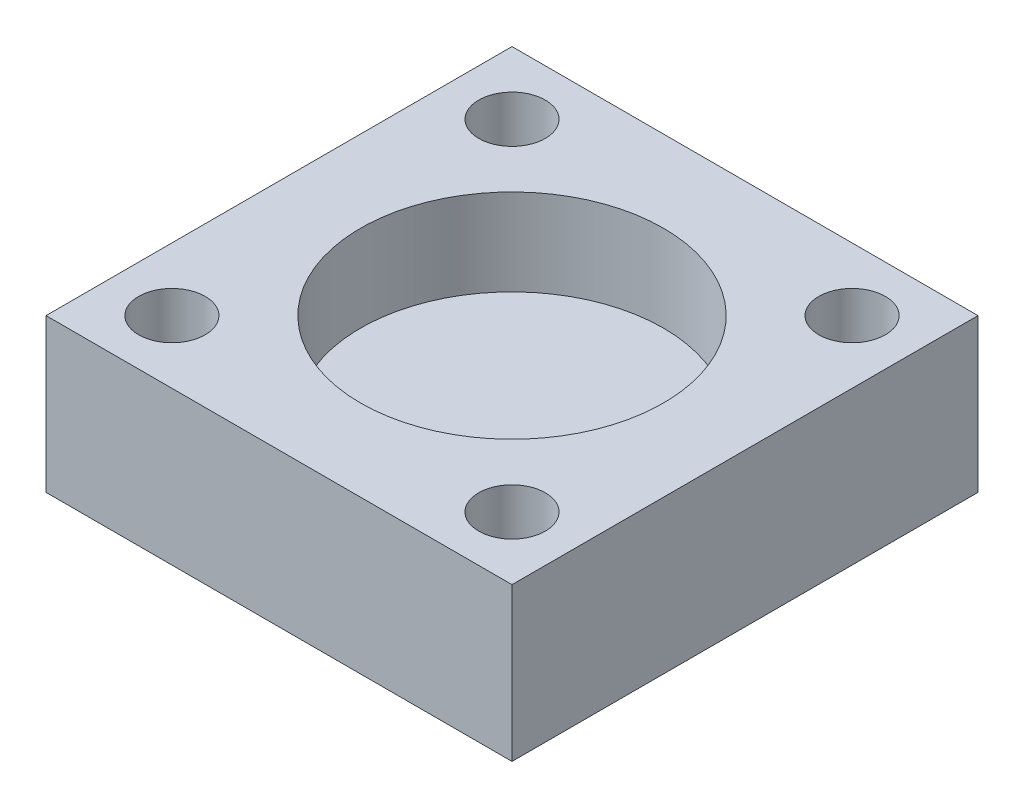
SolidWorks part; units mm, degrees
ref_plane "Front Plane" through (0, 0, 0) normal (0, 0, 1) x (1, 0, 0)
ref_plane "Top Plane" through (0, 0, 0) normal (0, 1, 0) x (1, 0, 0)
ref_plane "Right Plane" through (0, 0, 0) normal (1, 0, 0) x (0, 0, -1)
sketch "Sketch2" plane through (0, 0, 0) normal (0, 1, 0) x (1, 0, 0)
  line L1 (14, 14) -> (-14, 14)
  line L2 (14, 14) -> (14, -14)
  line L3 (14, -14) -> (-14, -14)
  line L4 (-14, 14) -> (-14, -14)
  line L5 (14, 14) -> (-14, -14) construction
  line L6 (14, -14) -> (-14, 14) construction
  circle A0 centre (0, 0) radius 9.1
  point P0 (0, 0)
  dimension "D1" = 18.2
  dimension "D3" = 14
extrude "Boss-Extrude1" add sketch "Sketch2" along normal blind 5.2 contours L1 L4 L3 L2 A0 | A0 | L2 L1 L4 L3 region at (13.604, 0, 0)
extrude "Boss-Extrude2" add sketch "Sketch2<4>" against normal blind 4 contours A0 | L1 L4 L3 L2 A0 region at (13.604, 0, 0) region at (0, 0, 0)
sketch "Sketch2<4>" plane through (0, 0, 0) normal (0, 1, 0) x (1, 0, 0) same geometry as "Sketch2"
sketch "Sketch3" plane through (0, 5.2, 0) normal (0, 1, 0) x (1, 0, 0)
  line L0 (-14, 14) -> (-6.4347, 6.4347) construction
  line L1 (0, 14) -> (0, -14) construction
  line L2 (-14, 0) -> (14, 0) construction
  line L4 (14, 14) -> (-14, 14)
  line L5 (-14, 14) -> (-14, -14)
  line L6 (-14, -14) -> (14, -14)
  line L7 (14, -14) -> (14, 14)
  line L8 (14, 14) -> (-14, 14)
  line L9 (-14, 14) -> (-14, -14)
  line L10 (-14, -14) -> (14, -14)
  line L11 (14, -14) -> (14, 14)
  circle A0 centre (0, 0) radius 9.1 construction
  circle A1 centre (0, 0) radius 9.1
  circle A2 centre (-10.2173, 10.2173) radius 2
  circle A3 centre (-10.2173, -10.2173) radius 2
  circle A4 centre (10.2173, -10.2173) radius 2
  circle A5 centre (10.2173, 10.2173) radius 2
  dimension "D2" = 4
  dimension "D1" = 0
extrude "Cut-Extrude1" cut sketch "Sketch3" against normal through all contours A4 | A3 | A2 | A5 region at (-10.2173, 5.2, -10.2173) region at (-10.2173, 5.2, 10.2173) region at (10.2173, 5.2, 10.2173) region at (10.2173, 5.2, -10.2173)
sketch "Sketch4" plane through (0, 5.2, 0) normal (0, 1, 0) x (1, 0, 0)
  line L0 (-14, 0) -> (14, 0) construction
  line L1 (-14, 14) -> (-14, -14) construction
  line L2 (14, 14) -> (14, -14) construction
  line L3 (0, 14) -> (0, -14) construction
  line L4 (14, 14) -> (-14, 14) construction
  line L5 (14, -14) -> (-14, -14) construction
  circle A0 centre (10.2173, 10.2173) radius 2 construction
  circle A1 centre (10.2173, -10.2173) radius 2 construction
  circle A2 centre (-10.2173, -10.2173) radius 2 construction
  circle A3 centre (-10.2173, 10.2173) radius 2 construction
  circle A4 centre (10.2173, 10.2173) radius 2
  circle A5 centre (10.2173, -10.2173) radius 2
  circle A6 centre (-10.2173, -10.2173) radius 2
  circle A7 centre (-10.2173, 10.2173) radius 2
  circle A8 centre (-10.2173, 10.2173) radius 3
  circle A9 centre (-10.2173, -10.2173) radius 3
  circle A10 centre (10.2173, -10.2173) radius 3
  circle A11 centre (10.2173, 10.2173) radius 3
  dimension "D1" = 6
fillet "Fillet1" radius 1 4 edges at (10.2173, -4, 12.2173) (10.2173, -4, -8.2173) (-10.2173, -4, 12.2173) (-10.2173, -4, -8.2173)
equation "\"d\"= 18"
equation "\"h\"=5.2"
equation "\"D1@Sketch2\"=\"d\"+0.2"
equation "\"D3@Sketch2\"=\"d\"/2+5.00mm"
equation "\"D1@Boss-Extrude1\"=\"h\""
